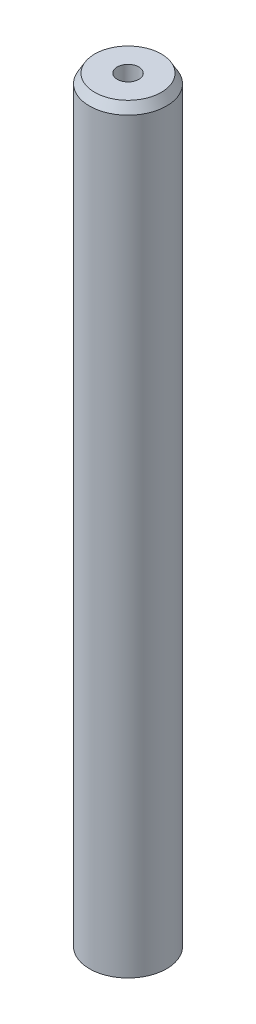
SolidWorks part; units mm, degrees
ref_plane "Front Plane" through (0, 0, 0) normal (0, 0, 1) x (1, 0, 0)
ref_plane "Top Plane" through (0, 0, 0) normal (0, 1, 0) x (1, 0, 0)
ref_plane "Right Plane" through (0, 0, 0) normal (1, 0, 0) x (0, 0, -1)
sketch "Sketch1" plane through (0, 0, 0) normal (0, 1, 0) x (1, 0, 0)
  circle A0 centre (0, 0) radius 5
  dimension "SHAFT_OD" = 10
extrude "Boss-Extrude1" add sketch "Sketch1" along normal blind 98.7223
sketch "Sketch2" plane through (0, 0, 0) normal (0, 1, 0) x (1, 0, 0)
  circle A0 centre (0, 0) radius 1.3991
  dimension "BORE_D" = 2.7982
extrude "Cut-Extrude1" cut sketch "Sketch2" along normal through all
chamfer "Chamfer1" distance 1.1875 angle 30 2 edges at (0, 98.7223, 5) (0, 0, 5) first distance on face at (0, 98.7223, 5) first distance on face at (0, 0, 1.3991)
